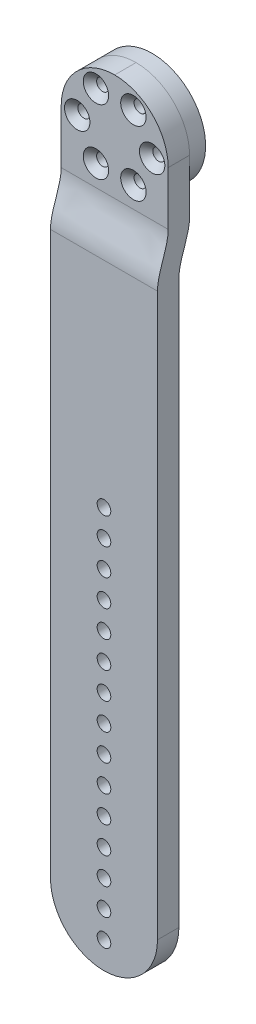
SolidWorks part; units mm, degrees
other "Markup1"
sketch "Sketch13" plane through (20, -53, 11) normal (0.0614, -0.6805, 0.7302) x (0.9699, -0.1321, -0.2046)
sketch "Sketch25" plane through (23.1, -99, 18.0001) normal (0.0614, -0.6805, 0.7302) x (0.9699, -0.1321, -0.2046)
sketch "Sketch26" plane through (23.1, -99, 18.0001) normal (0.0614, -0.6805, 0.7302) x (0.9699, -0.1321, -0.2046)
sketch "Sketch29" plane through (30, -126, 18.0001) normal (0.0614, -0.6805, 0.7302) x (0.9699, -0.1321, -0.2046)
sketch "Sketch31" plane through (30, -126, 18.0001) normal (0.0614, -0.6805, 0.7302) x (0.9699, -0.1321, -0.2046)
sketch "Sketch33" plane through (30, -136, 18.0001) normal (0.0614, -0.6805, 0.7302) x (0.9699, -0.1321, -0.2046)
sketch "Sketch39" plane through (30, -146, 18.0001) normal (0.0614, -0.6805, 0.7302) x (0.9699, -0.1321, -0.2046)
sketch "Sketch42" plane through (20.0001, -278, 18.0001) normal (0.0614, -0.6805, 0.7302) x (0.9699, -0.1321, -0.2046)
sketch "Sketch44" plane through (20, -268, 18.0001) normal (0.0614, -0.6805, 0.7302) x (0.9699, -0.1321, -0.2046)
other "Markup2"
sketch "Sketch30" plane through (30, 20, 18.0001) normal (0.1823, 0.1902, 0.9647) x (0.9812, 0.0279, -0.1909)
sketch "Sketch32" plane through (30, 20, 18.0001) normal (0.1823, 0.1902, 0.9647) x (0.9812, 0.0279, -0.1909)
sketch "Sketch34" plane through (30, 20, 18.0001) normal (0.1823, 0.1902, 0.9647) x (0.9812, 0.0279, -0.1909)
sketch "Sketch40" plane through (30, 20, 18.0001) normal (0.1823, 0.1902, 0.9647) x (0.9812, 0.0279, -0.1909)
sketch "Sketch43" plane through (20.0001, 20, 18.0001) normal (0.1823, 0.1902, 0.9647) x (0.9812, 0.0279, -0.1909)
sketch "Sketch45" plane through (20, 20, 18.0001) normal (0.1823, 0.1902, 0.9647) x (0.9812, 0.0279, -0.1909)
ref_plane "Front Plane" through (0, 0, 0) normal (0, 0, 1) x (1, 0, 0)
ref_plane "Top Plane" through (0, 0, 0) normal (0, 1, 0) x (1, 0, 0)
ref_plane "Right Plane" through (0, 0, 0) normal (1, 0, 0) x (0, 0, -1)
sketch "Sketch7" plane through (0, 0, 0) normal (0, 0, 1) x (1, 0, 0)
  line L1 (-20, 20) -> (20, 20)
  line L2 (-20, 20) -> (-20, -20)
  line L3 (-20, -20) -> (20, -20)
  line L4 (20, 20) -> (20, -20)
  line L5 (-20, 20) -> (20, -20) construction
  line L6 (-20, -20) -> (20, 20) construction
  point P0 (0, 0)
extrude "Boss-Extrude1" add sketch "Sketch7" along normal blind 14
ref_plane "Plane2" through (0, -22.1603, 5.9378) normal (0, -0.9659, 0.2588) x (1, 0, 0)
sketch "Sketch8" plane through (0, -20, 2.0782) normal (0, -1, 0) x (1, 0, 0)
  line L0 (20, 11.9218) -> (20, -2.0782) construction
  line L1 (-20, 11.9218) -> (20, 11.9218)
  line L2 (-20, 11.9218) -> (-20, 3.9218)
  line L3 (-20, 3.9218) -> (20, 3.9218)
  line L4 (20, 11.9218) -> (20, 3.9218)
  line L5 (0, 3.9218) -> (0, 11.9218) construction
  line L6 (-20, 7.9218) -> (20, 7.9218) construction
  line L7 (-20, -2.0782) -> (20, -2.0782) construction
  point P764 (0, 7.9218)
  dimension "D1" = 6
ref_plane "Plane4" through (0, -38, 0) normal (0, -1, 0) x (-1, 0, 0)
sketch "Sketch19" plane through (0, -38, 0) normal (0, -1, 0) x (-1, 0, 0)
  line L5 (20, -10) -> (-20, -10) construction
  line L6 (20, -18) -> (-20, -18)
  line L7 (20, -14) -> (20, 0) construction
  line L10 (20, -18) -> (20, -10)
  line L11 (20, -10) -> (-20, -10)
  line L12 (-20, -18) -> (-20, -10)
  line L13 (20, -18) -> (-20, -10) construction
  line L14 (20, -10) -> (-20, -18) construction
  point P0 (0, -14)
  dimension "D1" = 40
  dimension "D2" = 8
  dimension "D3" = 4
  dimension "D4" = 20
loft "Loft1" add profiles "Sketch19", "Sketch8<3>" start constraint normal to profile start tangent length 1 end constraint normal to profile end tangent length 1 connector at (-20, -38, 18) connector at (-20, -20, 14)
sketch "Sketch8<3>" plane through (0, -20, 2.0782) normal (0, -1, 0) x (1, 0, 0) same geometry as "Sketch8"
sketch "Sketch16" plane through (0, 0, 0) normal (0, 0, -1) x (-1, 0, 0)
  line L1 (24.5131, 32.6211) -> (-24.5131, 32.6211)
  line L2 (24.5131, 32.6211) -> (24.5131, -32.6211)
  line L3 (24.5131, -32.6211) -> (-24.5131, -32.6211)
  line L4 (-24.5131, 32.6211) -> (-24.5131, -32.6211)
  line L5 (24.5131, 32.6211) -> (-24.5131, -32.6211) construction
  line L6 (24.5131, -32.6211) -> (-24.5131, 32.6211) construction
  circle A0 centre (0, 0) radius 20
extrude "Cut-Extrude3" cut sketch "Sketch16" against normal blind 6
ref_plane "Plane3" [suppressed] through (0, -56, 0) normal (0, -1, 0) x (-1, 0, 0)
sketch "Sketch17" plane through (0, -38, 0) normal (0, -1, 0) x (-1, 0, 0)
  line L1 (20, -18) -> (-20, -18)
  line L2 (20, -18) -> (20, -10)
  line L3 (20, -10) -> (-20, -10)
  line L4 (-20, -18) -> (-20, -10)
  line L5 (20, -18) -> (-20, -10) construction
  line L6 (20, -10) -> (-20, -18) construction
  line L8 (-20, -18) -> (20, -18) construction
  line L9 (-20, -10) -> (-20, -18) construction
  dimension "D1" = 8
  dimension "D2" = 40
  dimension "D3" = 40
extrude "Boss-Extrude5" add sketch "Sketch17" along normal blind 230
sketch "Sketch10" plane through (0, 0, 14) normal (0, 0, 1) x (1, 0, 0)
  circle A0 centre (-7.0001, 12.1244) radius 2.25
  circle A1 centre (6.9999, 12.1244) radius 2.25
  circle A2 centre (13.9999, 0.0001) radius 2.25
  circle A3 centre (6.9999, -12.1243) radius 2.25
  circle A4 centre (-7.0001, -12.1243) radius 2.25
  circle A5 centre (-14.0001, 0.0001) radius 2.25
  point P0 (0, 0)
  point P1 (0.0025, 0.0011)
  dimension "D4" = 4.5
extrude "Cut-Extrude1" cut sketch "Sketch10" against normal blind 25
sketch "Sketch11" plane through (0, -268, -3.473) normal (0, 1, 0) x (1, 0, 0)
  line L0 (20, -21.473) -> (-20, -21.473) construction
  line L5 (30, -3.473) -> (-30, -3.473)
  line L6 (30, -3.473) -> (30, -21.473)
  line L7 (30, -21.473) -> (-30, -21.473)
  line L8 (-30, -3.473) -> (-30, -21.473)
  line L9 (30, -3.473) -> (-30, -21.473) construction
  line L10 (30, -21.473) -> (-30, -3.473) construction
  line L11 (-20, -13.473) -> (20, -13.473) construction
  point P0 (0, -12.473)
  point P9 (0, -13.473)
  dimension "D1" = 60
  dimension "D2" = 30
  dimension "D3" = 18
chamfer "Chamfer1" distance 2.5 angle 45 6 edges at (-4.7501, 12.1244, 14) (-11.7501, 0.0001, 14) (-4.7501, -12.1243, 14) (9.2499, 12.1244, 14) (16.2499, 0.0001, 14) (9.2499, -12.1243, 14)
fillet "Fillet3" radius 20 2 edges at (20, 20, 10) (-20, 20, 10)
fillet "Fillet4" radius 20 2 edges at (-20, -268, 14) (20, -268, 14)
sketch "Sketch41" plane through (0, 0, 0) normal (0, 0, 1) x (1, 0, 0)
  line L0 (-20, -248) -> (-20, -38) construction
  circle A0 centre (0, -258) radius 2.55
  dimension "D1" = 5.1
  dimension "D2" = 20
  dimension "D3" = 10
extrude "Cut-Extrude4" cut sketch "Sketch41" along normal blind 20
pattern_linear "LPattern1" count 15 spacing 10 along (0, 1, 0) of "Cut-Extrude4"
